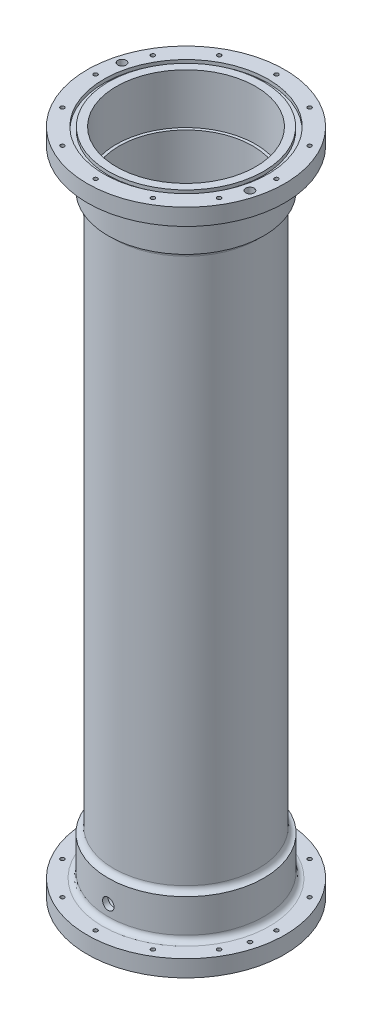
SolidWorks part; units mm, degrees
material "7075-T6 (SN)"
ref_plane "Front Plane" through (0, 0, 0) normal (0, 0, 1) x (1, 0, 0)
ref_plane "Top Plane" through (0, 0, 0) normal (0, 1, 0) x (1, 0, 0)
ref_plane "Right Plane" through (0, 0, 0) normal (1, 0, 0) x (0, 0, -1)
sketch "Sketch2" plane through (0, 0, 0) normal (0, 1, 0) x (1, 0, 0)
  circle A0 centre (0, 0) radius 38.1
  circle A1 centre (0, 0) radius 41.275
  dimension "D1" = 82.55
  dimension "D2" = 76.2
extrude "Base Cylinder" add sketch "Sketch2" along normal blind 381
sketch "Sketch3" plane through (0, 0, 0) normal (0, -1, 0) x (1, 0, 0)
  circle A0 centre (0, 0) radius 38.1
  circle A1 centre (0, 0) radius 56.3562
  dimension "D1" = 112.7125
extrude "Aft Flange" add sketch "Sketch3" against normal blind 9.525
sketch "Sketch34" plane through (0, 0, 0) normal (0, -1, 0) x (1, 0, 0)
  circle A0 centre (0, 0) radius 39.75
  dimension "D1" = 79.5
extrude "TemperatureInsert" cut sketch "Sketch34" against normal blind 28.575
sketch "Sketch6" plane through (0, 0, 0) normal (0, -1, 0) x (1, 0, 0)
  circle A0 centre (0, 0) radius 46.9011
  circle A1 centre (0, 0) radius 44.2849
  dimension "D1" = 93.8022
  dimension "D2" = 88.5698
extrude "Aft O-Ring" cut sketch "Sketch6" against normal blind 1.9812
sketch "Sketch33" plane through (0, 9.525, 0) normal (0, 1, 0) x (1, 0, 0)
  circle A0 centre (0, 0) radius 41.275
  circle A1 centre (0, 0) radius 44.45
  dimension "D1" = 82.55
  dimension "D2" = 88.9
extrude "CriticalBoss" add sketch "Sketch33" along normal blind 22.225
fillet "Fillet1" radius 3.175 2 edges at (0, 9.525, -44.45) (0, 31.75, 41.275)
sketch "Sketch For Bolt Holes" plane through (0, 0, 0) normal (0, -1, 0) x (1, 0, 0)
  circle A0 centre (-51.6255, 0) radius 1.5875
  circle A1 centre (-44.709, 25.8128) radius 1.5875
  circle A2 centre (-25.8128, 44.709) radius 1.5875
  circle A3 centre (0, 51.6255) radius 1.5875
  circle A4 centre (25.8127, 44.709) radius 1.5875
  circle A5 centre (44.709, 25.8128) radius 1.5875
  circle A6 centre (51.6255, 0) radius 1.5875
  circle A7 centre (44.709, -25.8127) radius 1.5875
  circle A8 centre (25.8128, -44.709) radius 1.5875
  circle A9 centre (0, -51.6255) radius 1.5875
  circle A10 centre (-25.8127, -44.709) radius 1.5875
  circle A11 centre (-44.709, -25.8128) radius 1.5875
  point P36 (0, 0)
  dimension "D2" = 3.175
  dimension "D1" = 51.6255
  dimension "D3" = 12
hole_wizard "Bolt Circle" positions "Sketch8" profile "Sketch9" hole size "#4-40" standard "ANSI Inch" end condition up to next
sketch "Sketch8" plane through (0, 0, 0) normal (0, -1, 0) x (-1, 0, 0)
  point P0 (-25.8127, -44.709)
  point P3 (-44.709, -25.8128)
  point P6 (-51.6255, 0)
  point P9 (-44.709, 25.8127)
  point P12 (-25.8128, 44.709)
  point P15 (0, 51.6255)
  point P18 (25.8127, 44.709)
  point P21 (44.709, 25.8128)
  point P24 (51.6255, 0)
  point P27 (44.709, -25.8128)
  point P30 (25.8128, -44.709)
  point P33 (0, -51.6255)
  point P36 (-25.8127, -44.709)
  point P38 (-44.709, -25.8128)
  point P40 (-51.6255, 0)
sketch "Sketch9" plane through (25.8127, 0, 44.709) normal (1, 0, 0) x (0, 0, -1)
  line L0 (0, 0) -> (0, 381)
  line L1 (0, 381) -> (1.1303, 381)
  line L2 (1.1303, 381) -> (1.1303, 0)
  line L5 (1.1303, 0) -> (0, 0)
  line L11 (0, -6.35) -> (0, 107.95) construction
  dimension "Thru Hole Dia." = 2.2606
  dimension "Thru Hole Depth" = 381
sketch "Dowel Hole Sketch" plane through (0, 0, 0) normal (0, -1, 0) x (1, 0, 0)
  line L0 (0, 0) -> (-51.6255, 0) construction
  line L1 (0, 0) -> (-49.8664, -13.3617) construction
  line L2 (0, 0) -> (0, -51.6255) construction
  line L3 (0, 0) -> (49.8664, 13.3617) construction
  circle A0 centre (0, 0) radius 51.6255
  circle A1 centre (-49.8664, -13.3617) radius 4.6172
  circle A2 centre (49.8664, 13.3617) radius 3.4532
  dimension "D1" = 15
hole_wizard "Hole1" positions "Sketch14" profile "Sketch12" legacy end condition up to next
sketch "Sketch14" plane through (0, 0, 0) normal (0, -1, 0) x (-1, 0, 0)
  point P0 (49.8664, 13.3617)
  point P3 (-49.8664, -13.3617)
sketch "Sketch12" plane through (-49.8664, 0, -13.3617) normal (1, 0, 0) x (0, 0, -1)
  line L0 (0, 0) -> (0, 381)
  line L1 (0, 381) -> (1.1906, 381)
  line L2 (1.1906, 381) -> (1.1906, 4.7625)
  line L3 (1.1906, 4.7625) -> (2.3813, 4.7625)
  line L4 (2.3813, 4.7625) -> (2.3813, 0)
  line L5 (2.3813, 0) -> (0, 0)
  line L6 (0, 110) -> (0, -10) construction
  dimension "Diameter" = 2.3813
  dimension "Depth" = 381
  dimension "C-Bore Diameter" = 4.7625
  dimension "C-Bore Depth" = 4.7625
ref_plane "Hoop Mid-Plane" through (0, 190.5, 0) normal (0, 1, 0) x (1, 0, 0)
ref_plane "PressureTapHolePlane" through (0, 0, 44.45) normal (0, 0, 1) x (1, 0, 0)
ref_plane "TemperatureTapPlane" through (0, 0, -44.45) normal (0, 0, 1) x (1, 0, 0)
sketch "ThermoHole" plane through (0, 0, -44.45) normal (0, 0, 1) x (1, 0, 0)
  line L0 (-56.3562, 0) -> (56.3562, 0) construction
  circle A0 centre (0, 19.05) radius 3.175
  dimension "D1" = 19.05
  dimension "D2" = 6.35
hole_wizard "1/8 NPT Tapped ThermocoupleHole" positions "Sketch43" profile "Sketch44" size "1/8" standard "ANSI Inch"
sketch "Sketch43" plane through (0, 0, -44.45) normal (0, 0, 1) x (1, 0, 0)
  line L0 (-56.3562, 0) -> (56.3562, 0) construction
  point P0 (0, 19.05)
  point P4 (0, 0)
  point P5 (0, 19.05)
  dimension "D1" = 19.05
sketch "Sketch44" plane through (0, 19.05, -44.45) normal (1, 0, 0) x (0, 1, 0)
  line L0 (0, 0) -> (0, 14.2175)
  line L1 (4.2164, 11.684) -> (0, 14.2175)
  line L2 (-4.2164, 11.684) -> (0, 14.2175) construction
  line L3 (4.2164, 11.684) -> (4.2164, 6.858)
  line L4 (4.2164, 6.858) -> (4.9362, 6.858)
  line L5 (4.9362, 6.858) -> (5.1415, 0)
  line L6 (-4.9362, 6.858) -> (-5.1415, 0) construction
  line L7 (5.1415, 0) -> (0, 0)
  line L8 (0, -6.35) -> (0, 107.95) construction
  line L11 (-4.2164, 6.858) -> (-4.9362, 6.858) construction
  dimension "Tap Drill Dia." = 8.4328
  dimension "Tap Drill Depth" = 11.684
  dimension "Thread Dia." = 10.283
  dimension "Thread Angle" = 3.43
  dimension "Thread Depth" = 6.858
  dimension "Drill Angle" = 118
mirror "Mirror1" about plane through (0, 190.5, 0) normal (0, 1, 0) of "Hole1", "Bolt Circle", "Fillet1", "CriticalBoss", "Aft O-Ring", "TemperatureInsert", "Aft Flange"
hole_wizard "5/16-18 Tapped Hole1" positions "Sketch48" profile "Sketch49" tap size "5/16-18" standard "ANSI Inch"
sketch "Sketch48" plane through (0, 0, 44.45) normal (0, 0, 1) x (1, 0, 0)
  line L0 (-56.3562, 0) -> (56.3562, 0) construction
  point P0 (0, 19.05)
  dimension "D1" = 19.05
sketch "Sketch49" plane through (0, 19.05, 44.45) normal (1, 0, 0) x (0, -1, 0)
  line L0 (0, 0) -> (0, 5.1361)
  line L1 (0, 5.1361) -> (3.2639, 3.175)
  line L2 (3.2639, 3.175) -> (3.2639, 0)
  line L5 (3.2639, 0) -> (0, 0)
  line L10 (0, 5.1361) -> (-3.2639, 3.175) construction
  line L11 (0, -6.35) -> (0, 107.95) construction
  dimension "Tap Drill Dia." = 6.5278
  dimension "Tap Drill Depth" = 3.175
  dimension "Drill Angle" = 118
cosmetic thread "Hole Thread1" parameters "D1"=3.175, "D2"=7.9375
sketch "Sketch50" plane through (0, 0, 44.45) normal (0, 0, 1) x (1, 0, 0)
  circle A0 centre (0, 19.05) radius 0.7937
  dimension "D1" = 1.5875
extrude "Cut-Extrude1" cut sketch "Sketch50" against normal up to next
